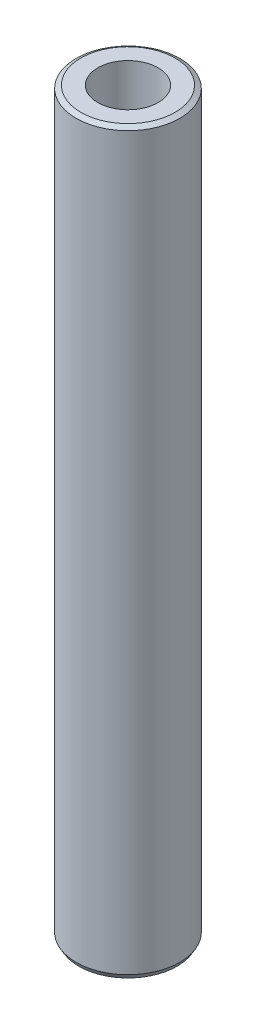
SolidWorks part; units mm, degrees
ref_plane "Front Plane" through (0, 0, 0) normal (0, 0, 1) x (1, 0, 0)
ref_plane "Top Plane" through (0, 0, 0) normal (0, 1, 0) x (1, 0, 0)
ref_plane "Right Plane" through (0, 0, 0) normal (1, 0, 0) x (0, 0, -1)
sketch "Sketch1" plane through (0, 0, 0) normal (0, 1, 0) x (1, 0, 0)
  circle A0 centre (0, 0) radius 37.5
  dimension "SHAFT_OD" = 75
extrude "Boss-Extrude1" add sketch "Sketch1" along normal blind 533.7169
sketch "Sketch2" plane through (0, 0, 0) normal (0, 1, 0) x (1, 0, 0)
  circle A0 centre (0, 0) radius 21.7997
  dimension "BORE_D" = 43.5994
extrude "Cut-Extrude1" cut sketch "Sketch2" along normal through all
chamfer "Chamfer1" distance 1.996 angle 60 2 edges at (0, 533.7169, 37.5) (0, 0, 37.5) first distance on face at (0, 533.7169, 37.5) first distance on face at (0, 0, 21.7997)
